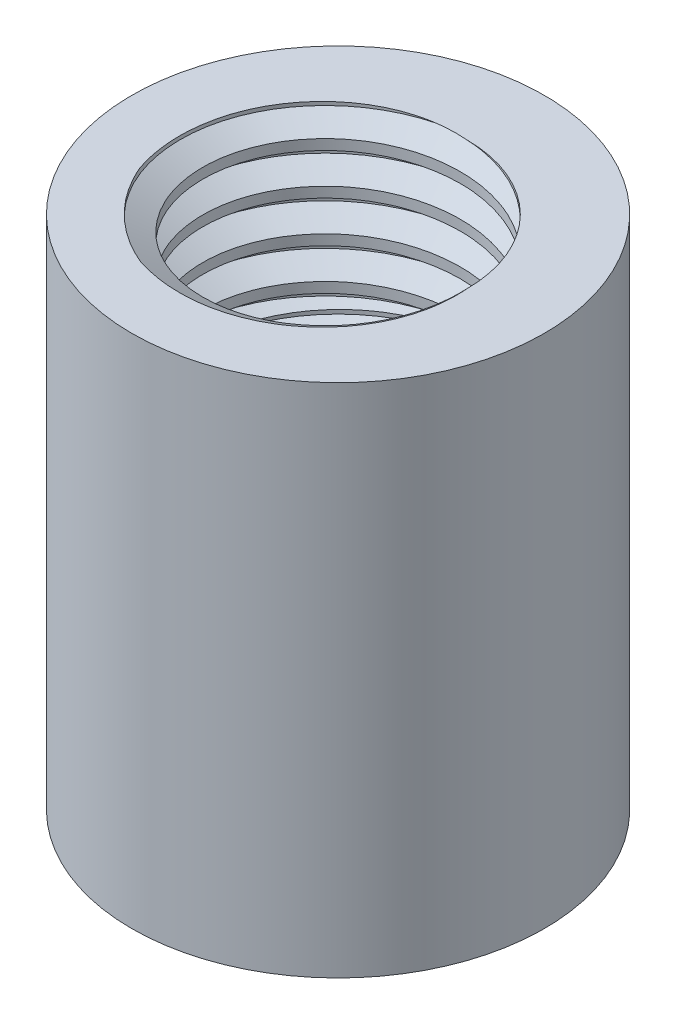
SolidWorks part; units mm, degrees
material "ABS"
ref_plane "Front Plane" through (0, 0, 0) normal (0, 0, 1) x (1, 0, 0)
ref_plane "Top Plane" through (0, 0, 0) normal (0, 1, 0) x (1, 0, 0)
ref_plane "Right Plane" through (0, 0, 0) normal (1, 0, 0) x (0, 0, -1)
sketch "Sketch1" plane through (0, 0, 0) normal (0, 1, 0) x (1, 0, 0)
  circle A0 centre (0, 0) radius 4
  dimension "D1" = 8
extrude "Boss-Extrude1" add sketch "Sketch1" along normal blind 10
sketch "Sketch2" plane through (0, 10, 0) normal (0, 1, 0) x (1, 0, 0)
  circle A0 centre (0, 0) radius 2.5
  dimension "D1" = 5
extrude "Cut-Extrude1" cut sketch "Sketch2" against normal blind 4
thread "Thread1" pitch 0.8 method cut profile "Thread Profile1" start angle 0, offset 0, length 20, pitch 0.8, diameter 5
ref_plane "Plane1" through (2.5, 6, 0) normal (0, 0, 1) x (1, 0, 0)
sketch "Thread Profile1" plane through (2.5, 6, 0) normal (0, 0, 1) x (1, 0, 0)
  line L0 (0, 0) -> (0, 0.8) construction
  line L1 (0, 0) -> (0.433, 0.25)
  line L2 (0.433, 0.25) -> (0.433, 0.35)
  line L3 (0.433, 0.35) -> (0, 0.6)
  line L4 (0.433, 0.3) -> (0, 0.3) construction
  line L11 (0, 0) -> (0, 0.6)
  point P2 (0, 0)
  dimension "Pitch" = 0.8
  dimension "Profile_Angle" = 60
  dimension "Profile_Land" = 0.1
  dimension "Profile_Height" = 0.433
sketch "Sketch5" plane through (0, 0, 0) normal (0, 0, -1) x (-1, 0, 0)
  line L4 (-2.933, 6.35) -> (-2.933, 6.25)
  line L5 (-2.933, 6.25) -> (-2.5, 6)
  line L6 (-2.5, 6) -> (-2.5, 6.6)
  line L7 (-2.5, 6.6) -> (-2.933, 6.35)
  line L8 (-2.933, 6.35) -> (-2.933, 6.25)
  line L9 (-2.933, 6.25) -> (-2.5, 6)
  line L10 (-2.5, 6) -> (-2.5, 6.6)
  line L11 (-2.5, 6.6) -> (-2.933, 6.35)
  dimension "D1" = 0
revolve "Cut-Revolve1" cut sketch "Sketch5" angle 360 about axis through (0, 6, 0) along (0, 1, 0)
sketch "Sketch6" plane through (0, 0, 0) normal (0, -1, 0) x (1, 0, 0)
  line L0 (1, 2.2913) -> (1, -2.2913)
  arc A0 (1, 2.2913) -> (1, -2.2913) centre (0, 0) ccw
  dimension "D1" = 5
  dimension "D2" = 1
extrude "Cut-Extrude2" cut sketch "Sketch6" against normal blind 4
